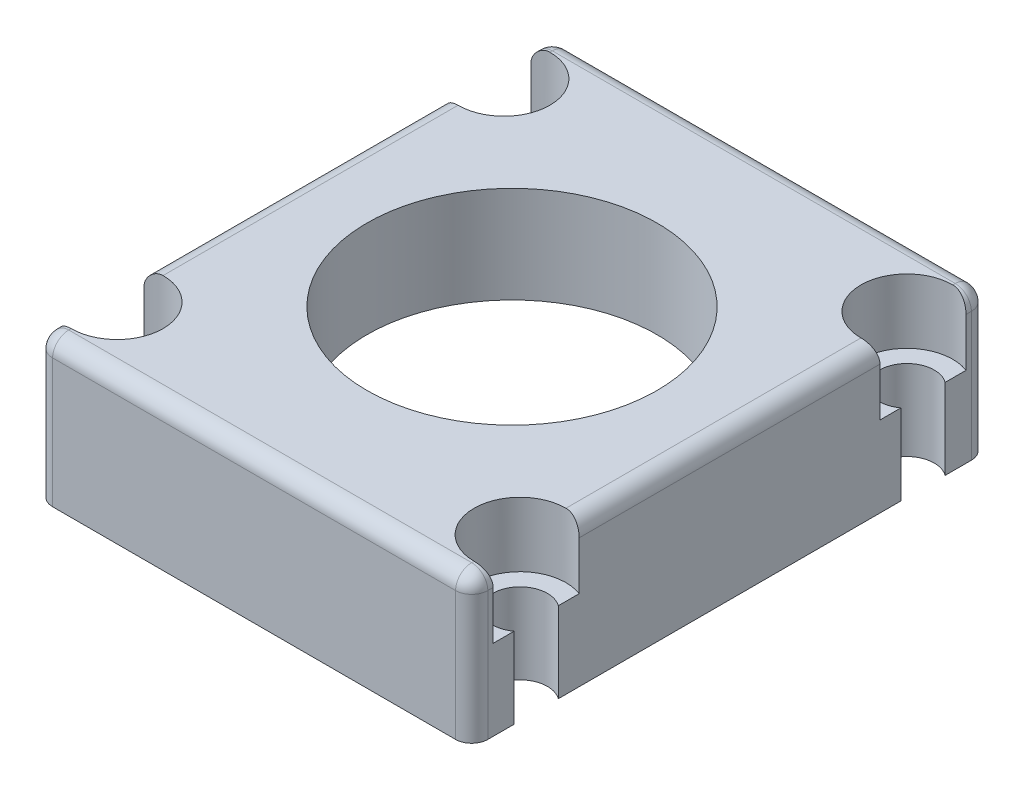
SolidWorks part; units mm, degrees
ref_plane "Front Plane" through (0, 0, 0) normal (0, 0, 1) x (1, 0, 0)
ref_plane "Top Plane" through (0, 0, 0) normal (0, 1, 0) x (1, 0, 0)
ref_plane "Right Plane" through (0, 0, 0) normal (1, 0, 0) x (0, 0, -1)
sketch "Sketch1" plane through (0, 0, 0) normal (0, 1, 0) x (1, 0, 0)
  line L0 (0, 0) -> (0, 15) construction
  line L1 (0, 15) -> (-12.5, 15) construction
  line L2 (-12.5, 15) -> (-12.5, -15) construction
  line L3 (-12.5, -15) -> (12.5, -15) construction
  line L4 (12.5, -15) -> (12.5, 15) construction
  line L5 (12.5, 15) -> (0, 15) construction
  line L6 (-12.5, 15) -> (-12.5, 12) construction
  line L7 (-12.5, -15) -> (-12.5, -12) construction
  line L8 (12.5, -15) -> (12.5, -12) construction
  line L9 (12.5, 15) -> (12.5, 12) construction
  circle A0 centre (-12.5, 12) radius 1.7
  circle A1 centre (12.5, 12) radius 1.7
  circle A2 centre (-12.5, -12) radius 1.7
  circle A3 centre (12.5, -12) radius 1.7
  dimension "D9" = 3.4
  dimension "D10" = 3.4
  dimension "D11" = 3.4
  dimension "D12" = 3.4
  dimension "D1" = 15
  dimension "D2" = 12.5
  dimension "D3" = 30
  dimension "D4" = 25
  dimension "D5" = 3
  dimension "D6" = 3
  dimension "D7" = 3
  dimension "D8" = 3
sketch "Sketch2" plane through (0, 0, 0) normal (0, 1, 0) x (1, 0, 0)
  line L1 (-13.5, -16) -> (13.5, -16)
  line L2 (-13.5, -16) -> (-13.5, 16)
  line L3 (-13.5, 16) -> (13.5, 16)
  line L4 (13.5, -16) -> (13.5, 16)
  line L5 (-13.5, -16) -> (13.5, 16) construction
  line L6 (-13.5, 16) -> (13.5, -16) construction
  circle A0 centre (0, 0) radius 9
  dimension "D1" = 18
  dimension "D2" = 27
  dimension "D3" = 32
extrude "Boss-Extrude1" add sketch "Sketch2" along normal blind 6
sketch "Sketch3" plane through (0, 0, 0) normal (0, -1, 0) x (1, 0, 0)
  line L1 (-13.5, -16) -> (13.5, -16)
  line L2 (-13.5, -16) -> (-13.5, 16)
  line L3 (-13.5, 16) -> (13.5, 16)
  line L4 (13.5, -16) -> (13.5, 16)
  line L5 (-13.5, -16) -> (13.5, 16) construction
  line L6 (-13.5, 16) -> (13.5, -16) construction
  line L7 (-12.5, -15) -> (12.5, -15)
  line L8 (-12.5, -15) -> (-12.5, 15)
  line L9 (-12.5, 15) -> (12.5, 15)
  line L10 (12.5, -15) -> (12.5, 15)
  line L11 (-12.5, -15) -> (12.5, 15) construction
  line L12 (-12.5, 15) -> (12.5, -15) construction
  point P0 (0, 0)
  point P7 (0, 0)
extrude "Boss-Extrude2" add sketch "Sketch3" along normal blind 3
extrude "Cut-Extrude1" cut sketch "Sketch1" against normal through all both and the other way through all
sketch "Sketch5" plane through (0, -3, 0) normal (0, -1, 0) x (1, 0, 0)
  line L0 (13.5, -10.6252) -> (13.5, -9.7087)
  line L1 (13.5, -10.6252) -> (13.5, 10.6252) construction
  line L2 (13.5, -13.3748) -> (13.5, -14.2913)
  line L3 (13.5, -16) -> (13.5, -13.3748) construction
  arc A2 (13.5, -10.6252) -> (13.5, -13.3748) centre (12.5, -12) ccw
  arc A3 (13.5, -9.7087) -> (13.5, -14.2913) centre (12.5, -12) ccw
  dimension "D1" = 5
extrude "Boss-Extrude4" add sketch "Sketch5" against normal up to next
mirror "Mirror1" about plane through (0, 0, 0) normal (1, 0, 0) of "Boss-Extrude4"
mirror "Mirror2" about plane through (0, 0, 0) normal (0, 0, 1) of "Mirror1", "Boss-Extrude4"
sketch "Sketch6" plane through (0, 6, 0) normal (0, 1, 0) x (1, 0, 0)
  circle A0 centre (12.5, 12) radius 2.85
  dimension "D1" = 5.7
extrude "Cut-Extrude2" cut sketch "Sketch6" against normal blind 4
mirror "Mirror3" about plane through (0, 0, 0) normal (1, 0, 0) of "Cut-Extrude2"
mirror "Mirror4" about plane through (0, 0, 0) normal (0, 0, 1) of "Mirror3", "Cut-Extrude2"
fillet "Fillet1" radius 1 6 edges at (13.5, 6, -15.3344) (13.5, 6, 15.3344) (-13.5, 6, 15.3344) (-13.5, 6, -15.3344) (0, 6, -16) (0, 6, 16)
sketch "Sketch11" plane through (0, 6, 0) normal (0, 1, 0) x (1, 0, 0)
  line L1 (-17.25, -16.75) -> (-7.75, -16.75)
  line L2 (-17.25, -16.75) -> (-17.25, -7.25)
  line L3 (-17.25, -7.25) -> (-7.75, -7.25)
  line L4 (-7.75, -16.75) -> (-7.75, -7.25)
  line L5 (-17.25, -16.75) -> (-7.75, -7.25) construction
  line L6 (-17.25, -7.25) -> (-7.75, -16.75) construction
  point P0 (-12.5, -12)
  dimension "D1" = 9.5
  dimension "D2" = 9.5
fillet "Fillet4" radius 1 8 edges at (13.5, 1, 16) (-13.5, 1, 16) (-13.5, 1, -16) (13.5, 1, -16) (13.2071, 5.7071, 15.7071) (-13.2071, 5.7071, 15.7071) (-13.2071, 5.7071, -15.7071) (13.2071, 5.7071, -15.7071)
